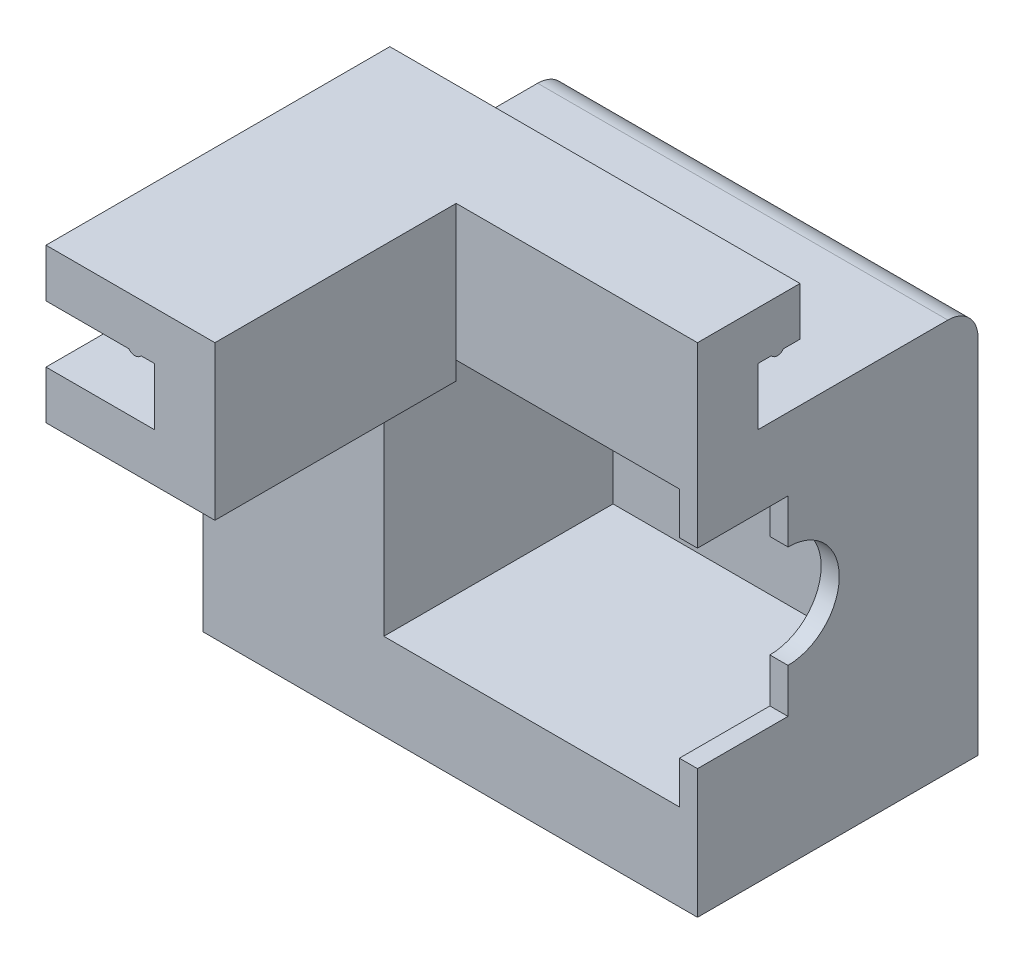
SolidWorks part; units mm, degrees
ref_plane "Front Plane" through (0, 0, 0) normal (0, 0, 1) x (1, 0, 0)
ref_plane "Top Plane" through (0, 0, 0) normal (0, 1, 0) x (1, 0, 0)
ref_plane "Right Plane" through (0, 0, 0) normal (1, 0, 0) x (0, 0, -1)
sketch "Sketch1" plane through (0, 0, 0) normal (0, 0, 1) x (1, 0, 0)
  line L0 (0, 0) -> (-18, 0)
  line L1 (-18, 0) -> (-18, -8)
  line L2 (-18, -8) -> (0, -8)
  line L3 (0, -8) -> (0, -17.5)
  line L4 (0, -17.5) -> (-18, -17.5)
  line L5 (-18, -17.5) -> (-18, -25.5)
  line L6 (-18, -25.5) -> (10, -25.5)
  line L7 (10, -25.5) -> (10, 0)
  line L8 (10, 0) -> (0, 0)
  arc A0 (-4.25, -8) -> (-2.25, -8) centre (-3.25, -7.25) ccw
  point P13 (-3.25, -8.5)
  dimension "D7" = 3.25
  dimension "D1" = 18
  dimension "D2" = 9.5
  dimension "D3" = 8
  dimension "D4" = 8
  dimension "D5" = 10
  dimension "D6" = 9
  dimension "D8" = 1
  dimension "D9" = 28
extrude "Boss-Extrude1" add sketch "Sketch1" along normal blind 50 contours L2 A0 | L7 L8 L0 L1 L2 L3 L4 L5 L6 region at (5, -0.3787, 0) region at (-3.25, -8.2039, 0)
sketch "Sketch2" plane through (0, 0, 0) normal (1, 0, 0) x (0, 0, -1)
  line L9 (0, 0) -> (0, -50) construction
  line L10 (7, -8) -> (0, -8)
  line L11 (0, -17.5) -> (7, -17.5)
  line L12 (0, -8) -> (0, -17.5)
  line L13 (7, -17.5) -> (7, -25.5)
  line L14 (7, -25.5) -> (-10, -25.5)
  line L15 (-10, -25.5) -> (-10, 0)
  line L16 (-10, 0) -> (0, 0)
  line L17 (0, 0) -> (7, 0)
  line L18 (7, 0) -> (7, -8)
  arc A1 (4.25, -8) -> (2.25, -8) centre (3.25, -7.25) cw
  dimension "D13" = 1.25
  dimension "D2" = 17
  dimension "D3" = 3.25
  dimension "D4" = 25.5
  dimension "D5" = 1
  dimension "D6" = 9.5
  dimension "D7" = 8
  dimension "D8" = 8
  dimension "D9" = 10
  dimension "D10" = 10
  dimension "D11" = 50
  dimension "D12" = 7
  dimension "D16" = 0.75
extrude "Boss-Extrude2" add sketch "Sketch2" along normal blind 50 contours L17 L9 L10 L18 | L9 L16 L15 L14 L12 | L11 L9 L14 L13 | A1 L10 region at (0, -4, -3.5) region at (0, -12.75, 5) region at (0, -21.5, -3.5) region at (0, -8.2039, -3.25)
extrude "Boss-Extrude3" add sketch "Sketch2<3>" against normal up to surface (18 mm away) contours L17 L9 L10 L18 | L11 L9 L14 L13 region at (0, -4, -3.5) region at (0, -21.5, -3.5) up to face at (-18, -4, 25)
sketch "Sketch2<3>" plane through (0, 0, 0) normal (1, 0, 0) x (0, 0, -1) same geometry as "Sketch2"
sketch "Sketch3" plane through (50, 0, 0) normal (1, 0, 0) x (0, 0, -1)
  line L0 (0, -17.5) -> (36.5, -17.5)
  line L1 (0, -25.5) -> (0, -88.5)
  line L2 (7, -25.5) -> (-10, -25.5) construction
  line L3 (0, -17.5) -> (0, -25.5)
  line L4 (36.5, -17.5) -> (36.5, -88.5)
  line L5 (36.5, -88.5) -> (0, -88.5)
  line L6 (0, -17.5) -> (-10, -17.5)
  line L7 (-10, -25.5) -> (-10, 0) construction
  line L8 (-10, -17.5) -> (-10, -88.5)
  line L9 (-10, -88.5) -> (0, -88.5)
  line M3 (-10, 0) -> (-10, -25.5)
  line M4 (-10, -25.5) -> (7, -25.5)
  line M5 (7, -25.5) -> (7, -17.5)
  line M6 (7, -17.5) -> (0, -17.5)
  dimension "D1" = 36.5
  dimension "D2" = 63
ref_plane "Wall" through (-32, 0, 0) normal (-1, 0, 0) x (0, 0, 1)
extrude "Boss-Extrude4" add sketch "Sketch3" against normal up to surface (82 mm away) contours L5 L4 L0 L1 M5 M4 | L8 L9 L1 M4 | L3 M6 M4 M5 | L3 L6 M3 M4 region at (50, -21.5, -3.5) region at (50, -21.5, 5) region at (50, -53.6957, -18.5758) region at (50, -57, 5) up to plane "Wall"
fillet "Fillet1" radius 5 3 edges at (-32, -53, -36.5) (-32, -17.5, -13.25) (9, -17.5, -36.5)
sketch "Sketch4" plane through (0, -88.5, 0) normal (0, -1, 0) x (1, 0, 0)
  line L0 (50, 10) -> (50, -19.5)
  line L1 (50, -36.5) -> (50, 10) construction
  line L2 (50, -19.5) -> (1, -19.5)
  line L3 (1, -19.5) -> (1, 10)
  line L4 (-18, 10) -> (10, 10) construction
  line L5 (1, 10) -> (50, 10)
  line L6 (-32, -31.5) -> (-32, 10) construction
  line L7 (-27, -36.5) -> (50, -36.5) construction
  dimension "D1" = 33
  dimension "D2" = 17
extrude "Cut-Extrude1" cut sketch "Sketch4" against normal up to surface (63 mm away) up to face at (-4, -25.5, 30)
sketch "Sketch5" plane through (50, 0, 0) normal (1, 0, 0) x (0, 0, -1)
  line L0 (-10, -36.5) -> (19.5, -36.5)
  line L1 (-10, -25.5) -> (-10, -88.5) construction
  line L2 (19.5, -25.5) -> (19.5, -88.5) construction
  line L3 (19.5, -36.5) -> (19.5, -77.5)
  line L4 (19.5, -77.5) -> (-10, -77.5)
  line L5 (-10, -77.5) -> (-10, -36.5)
  line L6 (0, -17.5) -> (31.5, -17.5) construction
  line L7 (-10, -36.5) -> (-10, -25.5)
  line L8 (-10, -25.5) -> (19.5, -25.5)
  line L9 (19.5, -25.5) -> (19.5, -36.5)
  line L10 (-10, -77.5) -> (-10, -88.5)
  line L11 (-10, -88.5) -> (19.5, -88.5)
  line L12 (19.5, -88.5) -> (19.5, -77.5)
  line M3 (-10, -25.5) -> (19.5, -25.5)
  line M4 (19.5, -25.5) -> (19.5, -88.5)
  dimension "D1" = 19
  dimension "D2" = 41
extrude "Boss-Extrude5" add sketch "Sketch5" against normal up to surface (49 mm away) contours L7 L0 M4 M3 | L10 L11 L4 M4 region at (50, -31, -4.75) region at (50, -83, -4.75) up to face at (1, -57, -4.75)
sketch "Sketch7" plane through (0, 0, 10) normal (0, 0, 1) x (1, 0, 0)
  line L0 (1, -36.5) -> (27, -36.5)
  line L1 (1, -36.5) -> (50, -36.5) construction
  line L2 (27, -36.5) -> (27, -26.5)
  line L3 (27, -26.5) -> (50, -26.5)
  line L4 (50, -36.5) -> (50, 0) construction
  line L5 (50, -26.5) -> (50, -88.5)
  line L6 (50, -88.5) -> (27, -88.5)
  line L7 (-32, -88.5) -> (50, -88.5) construction
  line L8 (27, -88.5) -> (27, -77.5)
  line L9 (1, -77.5) -> (50, -77.5) construction
  line L10 (27, -77.5) -> (1, -77.5)
  line L11 (1, -77.5) -> (1, -36.5)
  dimension "D1" = 26
  dimension "D2" = 26
  dimension "D3" = 10
extrude "Cut-Extrude2" cut sketch "Sketch7" against normal up to surface (29.5 mm away) up to face at (25.5, -57, -19.5)
sketch "Sketch6" plane through (27, 0, 0) normal (1, 0, 0) x (0, 0, -1)
  line L0 (-10, -36.5) -> (-10, -77.5) construction
  line L1 (36.5, -57) -> (-10, -57)
  line L2 (-1, -57) -> (19.5, -57)
  line L4 (9.25, -57) -> (9.25, -88.5)
  line L5 (36.5, -88.5) -> (19.5, -88.5) construction
  line L6 (4.25, -81.5) -> (14.25, -81.5)
  line L7 (36.5, -22.5) -> (36.5, -88.5) construction
  line L8 (0, -17.5) -> (31.5, -17.5) construction
  line L9 (19.5, -26.5) -> (19.5, -88.5) construction
  circle A0 centre (4.25, -81.5) radius 1.75
  circle A1 centre (14.25, -81.5) radius 1.75
  circle A2 centre (4.25, -81.5) radius 0.75
  circle A3 centre (14.25, -81.5) radius 0.75
  circle A4 centre (14.25, -32.5) radius 0.75
  circle A5 centre (14.25, -32.5) radius 1.75
  circle A6 centre (4.25, -32.5) radius 0.75
  circle A7 centre (4.25, -32.5) radius 1.75
  point P16 (9.25, -81.5)
  dimension "D4" = 3.5
  dimension "D5" = 1.5
  dimension "D6" = 1.5
  dimension "D7" = 3.5
  dimension "D1" = 24.5
  dimension "D2" = 24.5
  dimension "D3" = 10
  dimension "D8" = 20.5
  dimension "D9" = 39.5
  dimension "D10" = 0
extrude "Cut-Extrude3" cut sketch "Sketch6" against normal blind 5 contours A7 A6 | A6 | A5 A4 | A4 | A2 A0 | A2 | A3 A1 | A3 region at (27, -81.5, -2.5495) region at (27, -80.7712, -14.25) region at (27, -79.7995, -14.25) region at (27, -81.5, -3.5212) region at (27, -32.5, -14.25) region at (27, -32.5, -12.5495) region at (27, -32.5, -4.25) region at (27, -32.5, -2.5495)
extrude "Cut-Extrude4" cut sketch "Sketch6<6>" against normal blind 15 contours A6 | A4 | A2 | A3 region at (27, -81.5, -3.5212) region at (27, -32.5, -14.25) region at (27, -32.5, -4.25)
sketch "Sketch6<6>" plane through (27, 0, 0) normal (1, 0, 0) x (0, 0, -1) same geometry as "Sketch6"
sketch "Sketch8" plane through (0, 0, -7) normal (0, 0, -1) x (-1, 0, 0)
  line L0 (0, -8) -> (18, -8)
  line L1 (18, -8) -> (18, -17.5)
  line L2 (-50, -17.5) -> (27, -17.5) construction
  line L3 (18, -17.5) -> (0, -17.5)
  line L4 (0, -17.5) -> (0, -8)
extrude "Cut-Extrude5" cut sketch "Sketch8" against normal blind 40
sketch "Sketch9" plane through (-18, 0, 0) normal (-1, 0, 0) x (0, 0, 1)
  line L0 (-7, -8) -> (0, -8)
  line L1 (0, -8) -> (0, -17.5)
  line L2 (0, -17.5) -> (-7, -17.5)
  line L3 (-31.5, -17.5) -> (10, -17.5) construction
  line L4 (-7, -17.5) -> (-7, -8)
extrude "Cut-Extrude6" cut sketch "Sketch9" against normal blind 45
sketch "Sketch10" plane through (0, 0, 10) normal (0, 0, 1) x (1, 0, 0)
  line L0 (1, -36.5) -> (11, -36.5)
  line L1 (1, -36.5) -> (27, -36.5) construction
  line L2 (11, -36.5) -> (11, -26.5)
  line L3 (11, -26.5) -> (1, -26.5)
  line L4 (1, -26.5) -> (1, -36.5)
  dimension "D1" = 10
  dimension "D2" = 10
extrude "Cut-Extrude7" cut sketch "Sketch10" against normal up to surface (29.5 mm away) up to face at (26.25, -57.25, -19.5)
sketch "Sketch11" plane through (0, 0, -19.5) normal (0, 0, 1) x (1, 0, 0)
  line L1 (27, -88.5) -> (50, -88.5) construction
  line L2 (37, -88.5) -> (50, -88.5)
  line L3 (50, -88.5) -> (50, -26.5)
  line L4 (50, -26.5) -> (37, -26.5)
  line L5 (50, -26.5) -> (27, -26.5) construction
  line L8 (37, -26.5) -> (37, -88.5)
  line L9 (27, -26.5) -> (27, -36.5) construction
  line L10 (37, -33.5) -> (50, -33.5)
  line L11 (37, -81.5) -> (50, -81.5)
  line M5 (27, -88.5) -> (50, -88.5)
  line M6 (50, -88.5) -> (50, -26.5)
  dimension "D1" = 10
  dimension "D2" = 7
  dimension "D3" = 7
extrude "Cut-Extrude8" cut sketch "Sketch11" against normal through all contours L8 L11 L3 L10 | L11 L8 M5 M6 region at (43.5, -85, -19.5) region at (43.5, -57.5, -19.5)
sketch "Sketch12" plane through (0, -88.5, 0) normal (0, -1, 0) x (1, 0, 0)
  line L0 (-32, -26.5) -> (-24, -26.5)
  line L1 (-32, -31.5) -> (-32, 10) construction
  line L2 (-24, -26.5) -> (-24, -36.5)
  line L3 (-27, -36.5) -> (37, -36.5) construction
  line L4 (-32, -26.5) -> (-32, -36.5)
  line L5 (-32, -36.5) -> (-24, -36.5)
  dimension "D1" = 8
  dimension "D2" = 10
extrude "Cut-Extrude9" cut sketch "Sketch12" against normal through all
sketch "Sketch13" plane through (-32, 0, 0) normal (-1, 0, 0) x (0, 0, 1)
  line L4 (-26.5, -17.5) -> (-36.5, -17.5)
  line L5 (-36.5, -17.5) -> (-36.5, -23.5)
  line L6 (-36.5, -23.5) -> (-26.5, -23.5)
  line L7 (-26.5, -17.5) -> (-26.5, -88.5) construction
  line L8 (-26.5, -23.5) -> (-26.5, -17.5)
  dimension "D1" = 6
  dimension "D2" = 10
extrude "Cut-Extrude10" cut sketch "Sketch13" against normal up to surface (14 mm away) up to face at (-18, -21.5, 30)
sketch "Sketch14" plane through (0, 0, 10) normal (0, 0, 1) x (1, 0, 0)
  line L10 (10, -17.5) -> (16, -17.5)
  line L11 (10, -25.5) -> (10, 0) construction
  line L12 (16, -17.5) -> (16, -23.5)
  line L13 (16, -23.5) -> (10, -23.5)
  line L14 (10, -23.5) -> (10, -17.5)
  dimension "D1" = 6
  dimension "D2" = 6
sketch "Sketch15" plane through (0, 0, -26.5) normal (0, 0, -1) x (-1, 0, 0)
  line L0 (18, -23.5) -> (18, -17.5)
  line L1 (18, -17.5) -> (32, -17.5)
  line L2 (32, -5.225) -> (32, 5.225) construction
  line L3 (32, -17.5) -> (32, -23.5)
  line L4 (32, -22.5) -> (32, -88.5) construction
  line L5 (32, -23.5) -> (18, -23.5)
extrude "Cut-Extrude11" cut sketch "Sketch15" against normal through all
fillet "Fillet2" radius 3 3 edges at (-28, -23.5, -26.5) (-24, -56, -26.5) (-24, -23.5, -31.5)
ref_plane "Adjustment" through (0, 0, -20) normal (0, 0, 1) x (1, 0, 0)
sketch "Sketch17" plane through (0, 0, 10) normal (0, 0, 1) x (1, 0, 0)
  line L0 (1, -26.5) -> (50, -26.5)
  line L1 (50, -26.5) -> (50, -88.5)
  line L2 (50, -88.5) -> (1, -88.5)
  line L3 (-32, -88.5) -> (27, -88.5) construction
  line L4 (1, -88.5) -> (1, -26.5)
extrude "Boss-Extrude6" add sketch "Sketch17" against normal up to surface (46.5 mm away) up to face at (7.5976, -40.2087, -36.5)
sketch "Sketch18" plane through (0, 0, 10) normal (0, 0, 1) x (1, 0, 0)
  line L0 (5, -88.5) -> (5, -25.5)
  line L1 (-32, -88.5) -> (50, -88.5) construction
  line L2 (-18, -25.5) -> (10, -25.5) construction
  line L3 (5, -25.5) -> (50, -25.5)
  line L4 (50, -88.5) -> (50, 0) construction
  line L5 (50, -25.5) -> (50, -88.5)
  line L6 (50, -88.5) -> (5, -88.5)
  line L7 (-32, -23.5) -> (-32, -88.5) construction
  dimension "D1" = 37
extrude "Cut-Extrude12" cut sketch "Sketch18" against normal up to surface (30 mm away) up to plane "Adjustment"
sketch "Sketch19" plane through (0, 0, -20) normal (0, 0, 1) x (1, 0, 0)
  line L0 (50, -25.5) -> (5, -25.5)
  line L1 (5, -25.5) -> (5, -88.5)
  line L2 (5, -88.5) -> (50, -88.5)
  line L3 (50, -88.5) -> (50, -25.5)
  line L4 (5, -29.5) -> (50, -29.5)
  line L5 (5, -61.15) -> (50, -61.15)
  line M4 (5, -88.5) -> (50, -88.5)
  line M5 (50, -88.5) -> (50, -25.5)
  line M6 (50, -25.5) -> (5, -25.5)
  line M7 (5, -25.5) -> (5, -88.5)
  dimension "D1" = 4
  dimension "D2" = 31.65
extrude "Boss-Extrude7" add sketch "Sketch19" along normal up to surface (30 mm away) contours L4 L3 M7 M6 | L5 M7 M4 M5 region at (27.5, -27.5, -20) region at (27.5, -74.825, -20) up to face at (-15, -45.8333, 10)
sketch "Sketch22" plane through (50, 0, 0) normal (1, 0, 0) x (0, 0, -1)
  line L0 (20, -29.5) -> (20, -61.15)
  line L1 (20, -45.325) -> (5, -45.325)
  line L2 (20, -29.5) -> (-10, -29.5)
  line L3 (-10, -29.5) -> (-10, -61.15)
  line L4 (-10, -61.15) -> (20, -61.15)
  line L5 (5, -61.15) -> (5, -29.5)
  circle A0 centre (5, -45.325) radius 8.5
  point P10 (5, -45.325)
  line M8 (20, -29.5) -> (20, -61.15)
  line M9 (20, -61.15) -> (-10, -61.15)
  dimension "D1" = 17
  dimension "D2" = 15
extrude "Boss-Extrude8" add sketch "Sketch22" against normal blind 3 contours A0 L5 L0 L1 M9 | A0 L1 L2 L5 M8 region at (50, -36.0601, -13.7228) region at (50, -54.5899, -13.7228)
sketch "Sketch24" plane through (0, 0, 10) normal (0, 0, 1) x (1, 0, 0)
  line L0 (-18, -23.5) -> (-32, -23.5)
  line L1 (-32, -23.5) -> (-32, -33.5)
  line L2 (-32, -23.5) -> (-32, -88.5) construction
  line L3 (-32, -33.5) -> (-18, -33.5)
  line L4 (-18, -33.5) -> (-18, -23.5)
  dimension "D1" = 10
extrude "Cut-Extrude15" cut sketch "Sketch24" against normal through all
sketch "Sketch26" plane through (0, 0, -20) normal (0, 0, 1) x (1, 0, 0)
  line L0 (5, -29.5) -> (47, -29.5)
  line L1 (47, -29.5) -> (47, -61.15)
  line L2 (47, -61.15) -> (5, -61.15)
  line L3 (5, -61.15) -> (5, -29.5)
extrude "Cut-Extrude16" cut sketch "Sketch26" against normal blind 8
sketch "Sketch27" plane through (0, -29.5, 0) normal (0, -1, 0) x (1, 0, 0)
  line L0 (5, 10) -> (5, -28)
  line L1 (5, -28) -> (47, -28)
  line L2 (47, -28) -> (47, 10)
  line L3 (5, 10) -> (50, 10) construction
  line L4 (47, 10) -> (5, 10)
extrude "Cut-Extrude17" cut sketch "Sketch27" against normal blind 7
sketch "Sketch28" plane through (0, -61.15, 0) normal (0, 1, 0) x (1, 0, 0)
  line L0 (5, 28) -> (47, 28)
  line L1 (47, 28) -> (47, -10)
  line L2 (5, -10) -> (50, -10) construction
  line L3 (47, -10) -> (5, -10)
  line L4 (5, -10) -> (5, 28)
extrude "Cut-Extrude18" cut sketch "Sketch28" against normal blind 7
sketch "Sketch29" plane through (5, 0, 0) normal (1, 0, 0) x (0, 0, -1)
  line L0 (28, -22.5) -> (-10, -22.5)
  line L1 (-10, -22.5) -> (-10, -68.15)
  line L2 (-10, -68.15) -> (28, -68.15)
  line L3 (28, -68.15) -> (28, -22.5)
extrude "Cut-Extrude19" cut sketch "Sketch29" against normal blind 7
sketch "Sketch30" plane through (50, 0, 0) normal (1, 0, 0) x (0, 0, -1)
  line L0 (-10, -88.5) -> (-10, -82.5)
  line L1 (-10, -88.5) -> (-10, -61.15) construction
  line L2 (-10, -82.5) -> (36.5, -82.5)
  line L3 (36.5, -22.5) -> (36.5, -88.5) construction
  line L4 (36.5, -82.5) -> (36.5, -88.5)
  line L5 (36.5, -88.5) -> (-10, -88.5)
  dimension "D1" = 6
extrude "Cut-Extrude20" cut sketch "Sketch30" against normal through all
